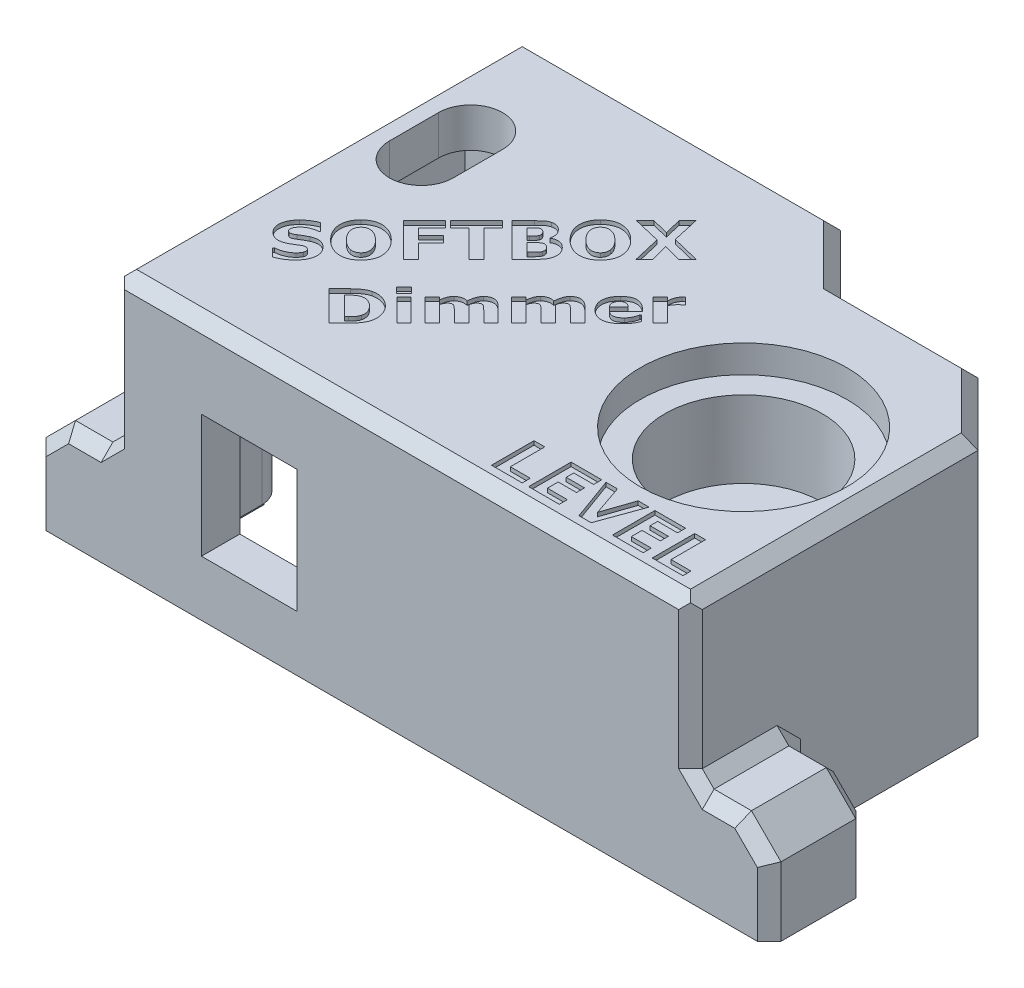
SolidWorks part; units mm, degrees
ref_plane "Спереди" through (0, 0, 0) normal (0, 0, 1) x (1, 0, 0)
ref_plane "Сверху" through (0, 0, 0) normal (0, 1, 0) x (1, 0, 0)
ref_plane "Справа" through (0, 0, 0) normal (1, 0, 0) x (0, 0, -1)
sketch "Эскиз1" plane through (0, 0, 0) normal (0, 1, 0) x (1, 0, 0)
  line L1 (-29.35, 20.8) -> (29.35, 20.8)
  line L2 (-29.35, 20.8) -> (-29.35, -20.8)
  line L3 (-29.35, -20.8) -> (29.35, -20.8)
  line L4 (29.35, 20.8) -> (29.35, -20.8)
  line L5 (-29.35, 20.8) -> (29.35, -20.8) construction
  line L6 (-29.35, -20.8) -> (29.35, 20.8) construction
  point P0 (0, 0)
  dimension "D1" = 58.7
  dimension "D2" = 41.6
extrude "Бобышка-Вытянуть1" add sketch "Эскиз1" along normal blind 26.4
sketch "Эскиз2" plane through (0, 0, 0) normal (0, -1, 0) x (1, 0, 0)
  line L0 (2.145, -18.8) -> (8.145, -12.8)
  line L1 (-27.35, 16.9) -> (27.35, 16.9)
  line L2 (-27.35, 16.9) -> (-27.35, -18.8)
  line L3 (-27.35, -18.8) -> (2.145, -18.8)
  line L4 (27.35, 16.9) -> (27.35, -7.595)
  line L5 (-27.35, 16.9) -> (28.5846, -19.2741) construction
  line L6 (-27.35, -18.8) -> (27.35, 16.9) construction
  line L7 (8.145, -12.8) -> (22.145, -12.8)
  line L8 (22.145, -12.8) -> (27.35, -7.595)
  line L9 (-29.35, -20.8) -> (-29.35, 20.8) construction
  line L11 (29.35, 20.8) -> (29.35, -20.8) construction
  line L12 (8, -12.45) -> (2, -18.45) construction
  line L13 (22, -12.45) -> (8, -12.45) construction
  line L14 (27, -7.45) -> (22, -12.45) construction
  line L16 (29.35, -20.8) -> (-29.35, -20.8) construction
  line L17 (-29.35, 20.8) -> (29.35, 20.8) construction
  point P0 (0.1248, -0.8686)
  point P22 (0, 0)
  dimension "D1" = 2
  dimension "D2" = 2
  dimension "D3" = 2
  dimension "D4" = 0.35
  dimension "D5" = 0.35
  dimension "D6" = 0.35
  dimension "D7" = 3.9
extrude "Вырез-Вытянуть1" cut sketch "Эскиз2" against normal offset from surface (22.4 mm away) 4 contours L7 L8 L4 L1 L2 L3 L0 up to face at (0, 26.4, 0)
sketch "Эскиз3" plane through (0, 0, 20.8) normal (0, 0, 1) x (1, 0, 0)
  line L0 (-11, 6) -> (-11, 17.8) construction
  line L1 (-20.35, 18.15) -> (-10.65, 18.15)
  line L2 (-20.35, 18.15) -> (-20.35, 5.65)
  line L3 (-20.35, 5.65) -> (-10.65, 5.65)
  line L4 (-10.65, 18.15) -> (-10.65, 5.65)
  line L5 (-11, 17.8) -> (-20, 17.8) construction
  line L6 (-20, 17.8) -> (-20, 6) construction
  line L7 (-20, 6) -> (-11, 6) construction
  dimension "D1" = 0.35
  dimension "D2" = 0.35
  dimension "D3" = 0.35
  dimension "D4" = 0.35
extrude "Вырез-Вытянуть2" cut sketch "Эскиз3" against normal up to surface (3.9 mm away) up to face at (0, 11.2, 16.9)
sketch "Эскиз4" plane through (-29.35, 0, 0) normal (-1, 0, 0) x (0, 0, 1)
  line L0 (-20.8, 0) -> (20.8, 0) construction
  line L1 (-1.55, 5.1) -> (-1.55, 13)
  line L2 (-4.6257, 0) -> (7.45, 0)
  line L3 (6.95, 1.3) -> (6.95, 4.6) construction
  line L4 (-1.55, 5.1) -> (7.45, 5.1)
  line L5 (7.45, 0) -> (7.45, 5.1)
  line L6 (-1.55, 13) -> (-12.55, 13)
  line L7 (-12.55, 13) -> (-12.55, 0)
  line L8 (-12.55, 0) -> (7.45, 0)
  line L9 (6.95, 4.6) -> (-3.35, 4.6) construction
  line L10 (-2.05, 12.5) -> (-2.05, 6) construction
  line L11 (-12.05, 12.5) -> (-2.05, 12.5) construction
  line L12 (-12.05, 12.5) -> (-12.05, 6) construction
  point P17 (-7.05, 12.5)
  line M6 (-20.8, 0) -> (20.8, 0)
  dimension "D1" = 0.5
  dimension "D2" = 0.5
  dimension "D3" = 0.5
  dimension "D4" = 0.5
  dimension "D5" = 0.5
extrude "Вырез-Вытянуть3" cut sketch "Эскиз4" against normal up to surface (2 mm away) contours L6 L7 L5 L4 L1 M6 up to face at (-27.35, 11.2, -0.95)
sketch "Эскиз5" plane through (0, 26.4, 0) normal (0, 1, 0) x (1, 0, 0)
  line L0 (-23.35, 2.05) -> (-23.35, 12.05) construction
  line L1 (-25.8, 2.05) -> (-20.9, 2.05) construction
  line L2 (-20.9, 12.05) -> (-25.8, 12.05) construction
  line L3 (-26.5, 7.05) -> (-19.4, 7.05) construction
  line L4 (-26.5, 12.05) -> (-26.5, 2.05) construction
  line L5 (-19.4, 12.05) -> (-19.4, 2.05) construction
  line L6 (-23.35, 4.55) -> (-23.35, 9.55) construction
  line L7 (-26.6, 4.55) -> (-26.6, 9.55)
  line L8 (-20.1, 4.55) -> (-20.1, 9.55)
  arc A0 (-26.6, 4.55) -> (-20.1, 4.55) centre (-23.35, 4.55) ccw
  arc A1 (-20.1, 9.55) -> (-26.6, 9.55) centre (-23.35, 9.55) ccw
  point P14 (-23.35, 7.05)
  dimension "D1" = 6.5
extrude "Вырез-Вытянуть4" cut sketch "Эскиз5" against normal up to surface (4 mm away) up to face at (4.6336, 22.4, -5.285)
sketch "Эскиз6" plane through (-29.35, 0, 0) normal (-1, 0, 0) x (0, 0, 1)
  line L0 (-13.4201, 17.4) -> (20.8, 17.4) construction
  line L2 (20.8, 26.4) -> (20.8, 0) construction
  line L3 (-20.8, 26.4) -> (20.8, 26.4) construction
  text T0 "+ -" font "Verdana" height in points 19
  point P2 (-17.0373, 15)
  point P8 (0, 0)
  point P9 (-12.5948, 15)
  point P10 (0, 0)
  point P11 (-11.8162, 15)
  point P12 (-12.65, 15)
  point P13 (-13.4201, 15)
  dimension "D1" = 9
extrude "Вырез-Вытянуть5" cut sketch "Эскиз6" against normal blind 0.4
sketch "Эскиз7" plane through (0, 26.4, 0) normal (0, 1, 0) x (1, 0, 0)
  circle A0 centre (16.6, -2.65) radius 10.5
  dimension "D1" = 21
sketch "Эскиз8" plane through (0, 22.4, 0) normal (0, -1, 0) x (1, 0, 0)
  circle A0 centre (16.6, 2.65) radius 8
  circle A1 centre (16.6, 2.65) radius 10.5 construction
  circle A2 centre (16.6, 2.65) radius 10.5
  dimension "D1" = 16
extrude "Бобышка-Вытянуть2" add sketch "Эскиз8" along normal blind 9.6
sketch "Эскиз9" plane through (0, 12.8, 0) normal (0, -1, 0) x (1, 0, 0)
  circle A0 centre (16.6, 2.65) radius 10.5 construction
  circle A1 centre (16.6, 2.65) radius 10.5
extrude "Бобышка-Вытянуть3" add sketch "Эскиз9" against normal blind 3
extrude "Вырез-Вытянуть8" cut sketch "Эскиз7" against normal blind 2.8
sketch "Эскиз10" plane through (0, 23.6, 0) normal (0, 1, 0) x (1, 0, 0)
  circle A0 centre (16.6, -2.65) radius 8 construction
  circle A1 centre (16.6, -2.65) radius 8
extrude "Вырез-Вытянуть9" cut sketch "Эскиз10" against normal up to surface (1.2 mm away) up to face at (16.6, 22.4, 13.15)
sketch "Эскиз11" plane through (0, 26.4, 0) normal (0, 1, 0) x (1, 0, 0)
  line L0 (4.5635, -18.8) -> (29.35, -18.8) construction
  line L1 (29.35, -20.8) -> (29.35, 20.8) construction
  line L3 (-29.35, -20.8) -> (29.35, -20.8) construction
  text T0 " LEVEL" font "Verdana" height in points 16
  point P7 (4.5635, 10.8)
  dimension "D1" = 2
extrude "Вырез-Вытянуть10" cut sketch "Эскиз11" against normal blind 0.4
sketch "Эскиз12" plane through (0, 15.8, 0) normal (0, 1, 0) x (1, 0, 0)
  circle A0 centre (16.6, -2.65) radius 3.75
  dimension "D1" = 7.5
extrude "Вырез-Вытянуть11" cut sketch "Эскиз12" against normal up to surface (3 mm away) up to face at (16.6, 12.8, -7.85)
sketch "Эскиз13" plane through (0, 22.4, 0) normal (0, -1, 0) x (1, 0, 0)
  line L0 (-21.45, 13.55) -> (-21.45, 16.9)
  line L1 (-27.35, 16.9) -> (27.35, 16.9) construction
  line L2 (-21.45, 16.9) -> (-27.35, 16.9)
  line L3 (-27.35, 16.9) -> (-27.35, 11.1)
  line L4 (-27.35, 16.9) -> (-27.35, -18.8) construction
  line L5 (-27.35, 11.1) -> (-23.9, 11.1)
  line L6 (-23.9, -13) -> (-27.35, -13)
  line L7 (-27.35, -13) -> (-27.35, -18.8)
  line L8 (-27.35, -18.8) -> (-21.45, -18.8)
  line L9 (-27.35, -18.8) -> (2.145, -18.8) construction
  line L10 (-21.45, -18.8) -> (-21.45, -15.45)
  line L11 (21.45, 13.55) -> (21.45, 16.9)
  line L12 (21.45, 16.9) -> (27.35, 16.9)
  line L13 (27.35, 16.9) -> (27.35, 11.1)
  line L14 (27.35, 16.9) -> (27.35, -7.595) construction
  line L15 (27.35, 11.1) -> (23.9, 11.1)
  circle A0 centre (-23.9, 13.55) radius 1.25
  circle A1 centre (-23.9, -15.45) radius 1.25
  circle A2 centre (23.9, 13.55) radius 1.25
  arc A3 (-23.9, 11.1) -> (-21.45, 13.55) centre (-23.9, 13.55) ccw
  arc A4 (21.45, 13.55) -> (23.9, 11.1) centre (23.9, 13.55) ccw
  arc A5 (-21.45, -15.45) -> (-23.9, -13) centre (-23.9, -15.45) ccw
  dimension "D1" = 2.5
  dimension "D2" = 1.2
extrude "Бобышка-Вытянуть4" add sketch "Эскиз13" along normal blind 16.4
sketch "Эскиз14" plane through (0, 0, 0) normal (0, -1, 0) x (1, 0, 0)
  line L0 (2.9734, -20.8) -> (8.9734, -14.8)
  line L1 (29.35, -20.8) -> (-29.35, -20.8) construction
  line L2 (8.9734, -14.8) -> (22.9734, -14.8)
  line L3 (22.9734, -14.8) -> (29.35, -8.4234)
  line L4 (29.35, 20.8) -> (29.35, -20.8) construction
  line L5 (29.35, -8.4234) -> (29.35, -20.8)
  line L6 (29.35, -20.8) -> (2.9734, -20.8)
  line L7 (2.145, -18.8) -> (8.145, -12.8) construction
  line L8 (8.145, -12.8) -> (22.145, -12.8) construction
  line L9 (22.145, -12.8) -> (27.35, -7.595) construction
  dimension "D1" = 2
  dimension "D2" = 2
  dimension "D3" = 2
extrude "Вырез-Вытянуть12" cut sketch "Эскиз14" against normal up to surface (26.4 mm away) up to face at (16.6, 26.4, 13.15)
sketch "Эскиз15" plane through (-29.35, 0, 0) normal (-1, 0, 0) x (0, 0, 1)
  line L0 (-12.55, 13) -> (-12.55, 0) construction
  line L1 (-12.55, 13) -> (-12.55, 0)
  line L2 (7.45, 0) -> (7.45, 5.1) construction
  line L3 (-1.55, 5.1) -> (7.45, 5.1) construction
  line L4 (-1.55, 5.1) -> (-1.55, 13) construction
  line L5 (-1.55, 13) -> (-12.55, 13) construction
  line L6 (7.45, 0) -> (7.45, 5.1)
  line L7 (-1.55, 5.1) -> (7.45, 5.1)
  line L8 (-1.55, 5.1) -> (-1.55, 13)
  line L9 (-1.55, 13) -> (-12.55, 13)
  line L10 (-12.55, 0) -> (-14.05, 0)
  line L11 (-20.8, 0) -> (-12.55, 0) construction
  line L12 (-14.05, 0) -> (-14.05, 14.5)
  line L13 (-14.05, 14.5) -> (-0.05, 14.5)
  line L14 (-0.05, 14.5) -> (-0.05, 6.6)
  line L15 (-0.05, 6.6) -> (8.95, 6.6)
  line L16 (8.95, 6.6) -> (8.95, 0)
  line L17 (7.45, 0) -> (20.8, 0) construction
  line L18 (8.95, 0) -> (7.45, 0)
  dimension "D1" = 1.5
  dimension "D2" = 1.5
  dimension "D3" = 1.5
  dimension "D4" = 1.5
  dimension "D5" = 1.5
extrude "Бобышка-Вытянуть5" add sketch "Эскиз15" along normal blind 2
sketch "Эскиз16" plane through (0, 26.4, 0) normal (0, 1, 0) x (1, 0, 0)
  line L0 (-27.2654, -16.9484) -> (4.4105, 14.7275) construction
  text T0 "SOFTBOX" font "Verdana" height in points 18
extrude "Вырез-Вытянуть13" cut sketch "Эскиз16" against normal blind 0.4
sketch "Эскиз17" plane through (0, 26.4, 0) normal (0, 1, 0) x (1, 0, 0)
  line L0 (-17.486, -18.39) -> (8.034, 7.13) construction
  text T0 "Dimmer" font "Verdana" height in points 16
extrude "Вырез-Вытянуть14" cut sketch "Эскиз17" against normal blind 0.4
sketch "Эскиз18" plane through (0, 0, 20.8) normal (0, 0, 1) x (1, 0, 0)
  line L0 (29.35, 10) -> (34.35, 10)
  line L1 (29.35, 26.4) -> (29.35, 0) construction
  line L2 (34.35, 10) -> (37.35, 7)
  line L3 (37.35, 7) -> (37.35, 0)
  line L4 (37.35, 0) -> (29.35, 0)
  line L5 (29.35, 0) -> (29.35, 10)
  line L6 (0, 26.4) -> (0, 0) construction
  line L7 (-29.35, 26.4) -> (29.35, 26.4) construction
  line L8 (-29.35, 0) -> (29.35, 0) construction
  line L9 (-37.35, 0) -> (-29.35, 0)
  line L10 (-37.35, 7) -> (-37.35, 0)
  line L11 (-34.35, 10) -> (-37.35, 7)
  line L12 (-29.35, 10) -> (-34.35, 10)
  line L13 (-29.35, 0) -> (-29.35, 10)
  dimension "D1" = 8
  dimension "D2" = 10
  dimension "D3" = 45
  dimension "D4" = 5
extrude "Бобышка-Вытянуть6" add sketch "Эскиз18" against normal blind 10
sketch "Эскиз19" plane through (0, 0, 0) normal (0, -1, 0) x (1, 0, 0)
  line L0 (-37.35, 15.8) -> (37.35, 15.8) construction
  line L1 (-37.35, 10.8) -> (-37.35, 20.8) construction
  line L2 (37.35, 10.8) -> (37.35, 20.8) construction
  line L3 (0, 20.8) -> (0, -20.8) construction
  line L4 (-37.35, 20.8) -> (37.35, 20.8) construction
  line L5 (2.9734, -20.8) -> (-29.35, -20.8) construction
  line L6 (-32.35, 20.8) -> (-32.35, 10.8) construction
  circle A0 centre (-32.35, 15.8) radius 1.4
  circle A1 centre (32.35, 15.8) radius 1.4
  point P17 (0, 0)
  dimension "D2" = 2.8
  dimension "D1" = 5
extrude "Вырез-Вытянуть15" cut sketch "Эскиз19" against normal blind 4
chamfer "Фаска1" distance 1.2 angle 45 7 edges at (29.35, 26.4, 6.1883) (26.1617, 26.4, -11.6117) (15.9734, 26.4, -14.8) (5.9734, 26.4, -17.8) (-13.1883, 26.4, -20.8) (-29.35, 26.4, 0) (0, 26.4, 20.8)
chamfer "Фаска2" distance 1.2 angle 45 18 edges at (37.35, 3.5, 20.8) (37.35, 3.5, 10.8) (35.85, 8.5, 20.8) (35.85, 8.5, 10.8) (29.35, 5, 10.8) (31.85, 10, 20.8) (31.85, 10, 10.8) (29.35, 10, 15.8) (29.35, 17.6, 20.8) (-29.35, 5, 10.8) (-29.35, 17.6, 20.8) (-37.35, 3.5, 10.8) (-35.85, 8.5, 10.8) (-31.85, 10, 10.8) (-37.35, 3.5, 20.8) (-35.85, 8.5, 20.8) (-31.85, 10, 20.8) (-29.35, 10, 15.8)
chamfer "Фаска3" distance 2 angle 45 4 edges at (-29.35, 7.25, -14.05) (-29.35, 14.5, -7.05) (-29.35, 10.55, -0.05) (-29.35, 6.6, 4.45)
sketch "Эскиз20" plane through (0, 12.8, 0) normal (0, -1, 0) x (1, 0, 0)
  line L0 (17.6, 9.05) -> (17.6, 8.65) construction
  line L1 (15.25, 9.4) -> (17.95, 9.4)
  line L2 (15.25, 9.4) -> (15.25, 8.3)
  line L3 (15.25, 8.3) -> (17.95, 8.3)
  line L4 (17.95, 9.4) -> (17.95, 8.3)
  line L5 (10.6, 8.65) -> (22.6, 8.65) construction
  line L6 (15.6, 9.05) -> (17.6, 9.05) construction
  line L7 (15.6, 8.65) -> (15.6, 9.05) construction
  dimension "D1" = 0.35
  dimension "D2" = 0.35
  dimension "D3" = 0.35
  dimension "D4" = 0.35
extrude "Вырез-Вытянуть16" cut sketch "Эскиз20" against normal blind 2
